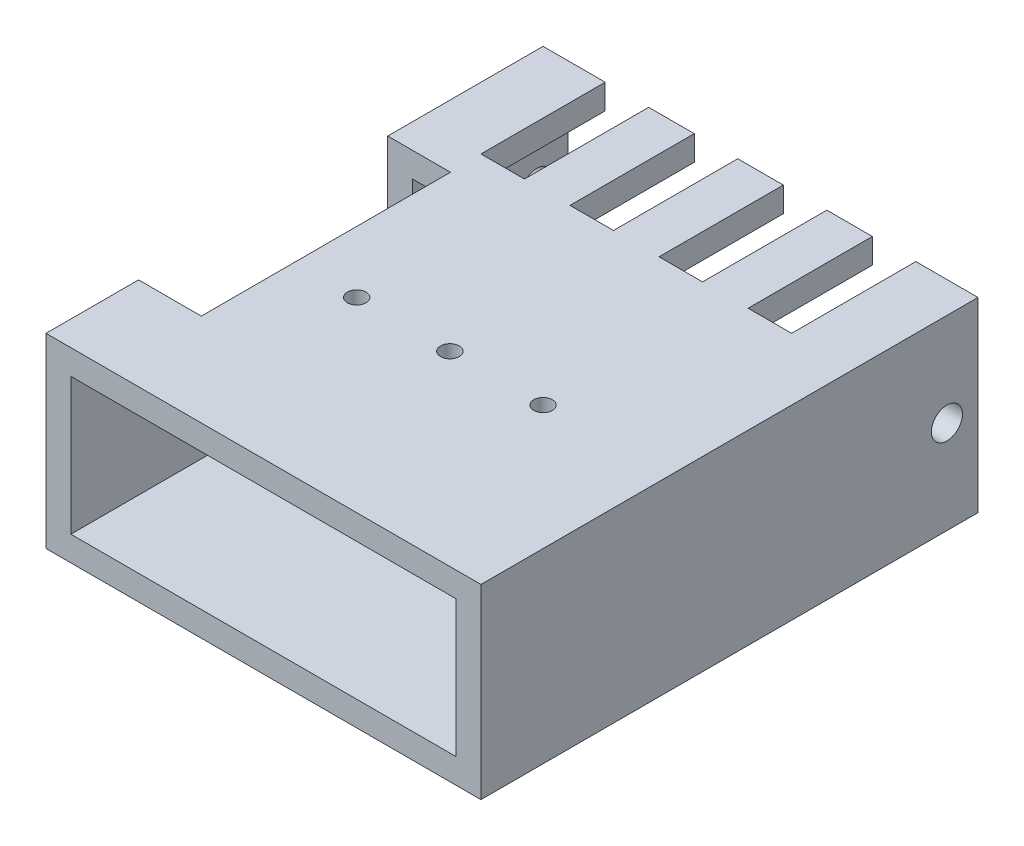
SolidWorks part; units mm, degrees
ref_plane "Front Plane" through (0, 0, 0) normal (0, 0, 1) x (1, 0, 0)
ref_plane "Top Plane" through (0, 0, 0) normal (0, 1, 0) x (1, 0, 0)
ref_plane "Right Plane" through (0, 0, 0) normal (1, 0, 0) x (0, 0, -1)
sketch "Sketch1" plane through (0, 0, 0) normal (0, 1, 0) x (1, 0, 0)
  line L1 (0, 0) -> (88.9, 0)
  line L2 (0, 0) -> (0, 101.6)
  line L3 (0, 101.6) -> (88.9, 101.6)
  line L4 (88.9, 0) -> (88.9, 101.6)
  dimension "D1" = 101.6
  dimension "D2" = 88.9
extrude "Boss-Extrude1" add sketch "Sketch1" along normal blind 38.1 contours L1 L4 L3 L2
shell "Shell1" thickness 5.08 removed face at (44.45, 19.05, -101.6) removed face at (44.45, 19.05, 0)
sketch "Sketch4" plane through (0, 0, 0) normal (0, -1, 0) x (1, 0, 0)
  line L0 (0, 0) -> (0, -101.6) construction
  line L1 (0, -18.923) -> (12.827, -18.923)
  line L2 (0, -18.923) -> (0, -69.85)
  line L3 (0, -69.85) -> (12.827, -69.85)
  line L4 (12.827, -18.923) -> (12.827, -69.85)
  line L5 (0, -101.6) -> (88.9, -101.6) construction
  point P5 (0, 0)
  point P10 (12.827, -25.273)
  dimension "D1" = 50.927
  dimension "D2" = 12.827
  dimension "D3" = 31.75
extrude "Cut-Extrude3" cut sketch "Sketch4" against normal through all from offset 19.05 offset against normal yes
sketch "Sketch5" plane through (0, 38.1, 0) normal (0, 1, 0) x (1, 0, 0)
  line L0 (0, 101.6) -> (88.9, 101.6) construction
  line L1 (12.7, 101.6) -> (21.59, 101.6)
  line L2 (12.7, 101.6) -> (12.7, 76.2)
  line L3 (12.7, 76.2) -> (21.59, 76.2)
  line L4 (21.59, 101.6) -> (21.59, 76.2)
  line L5 (30.9033, 101.6) -> (30.9033, 76.2)
  line L6 (30.9033, 101.6) -> (39.7933, 101.6)
  line L7 (39.7933, 101.6) -> (39.7933, 76.2)
  line L8 (30.9033, 76.2) -> (39.7933, 76.2)
  line L9 (49.1067, 101.6) -> (49.1067, 76.2)
  line L10 (49.1067, 101.6) -> (57.9967, 101.6)
  line L11 (57.9967, 101.6) -> (57.9967, 76.2)
  line L12 (49.1067, 76.2) -> (57.9967, 76.2)
  line L13 (67.31, 101.6) -> (67.31, 76.2)
  line L14 (67.31, 101.6) -> (76.2, 101.6)
  line L15 (76.2, 101.6) -> (76.2, 76.2)
  line L16 (67.31, 76.2) -> (76.2, 76.2)
  line L17 (12.7, 88.9) -> (76.2, 88.9) construction
  line L19 (12.7, 101.6) -> (5.08, 101.6) construction
  line L20 (0, 69.85) -> (0, 101.6) construction
  line L21 (76.2, 101.6) -> (83.82, 101.6) construction
  line L22 (88.9, 0) -> (88.9, 101.6) construction
  dimension "D1" = 25.4
  dimension "D2" = 8.89
  dimension "D4" = 5.08
  dimension "D5" = 5.08
  dimension "D6" = 63.5
  dimension "D3" = 4
extrude "Cut-Extrude4" cut sketch "Sketch5" against normal through all
sketch "Sketch6" plane through (0, 0, 0) normal (-1, 0, 0) x (0, 0, 1)
  line L0 (-101.6, 38.1) -> (-101.6, 0) construction
  circle A0 centre (-95.25, 19.05) radius 3.175
  point P4 (0, 0)
  point P5 (0, 0)
  point P6 (-101.6, 19.05)
  dimension "D1" = 6.35
  dimension "0.25" = 6.35
extrude "Cut-Extrude5" cut sketch "Sketch6" against normal through all and the other way blind 4.2672
sketch "Sketch7" plane through (0, 38.1, 0) normal (0, 1, 0) x (1, 0, 0)
  line L0 (0, 0) -> (88.9, 0) construction
  line L1 (49.1067, 76.2) -> (57.9967, 76.2) construction
  line L2 (25.4, 38.1) -> (63.5, 38.1) construction
  circle A0 centre (44.45, 38.1) radius 1.905
  circle A2 centre (25.4, 38.1) radius 1.905
  circle A3 centre (63.5, 38.1) radius 1.905
  point P4 (44.45, 0)
  point P11 (0, 0)
  dimension "D1" = 3.81
  dimension "D2" = 38.1
  dimension "D3" = 19.05
extrude "Cut-Extrude6" cut sketch "Sketch7" against normal up to next
